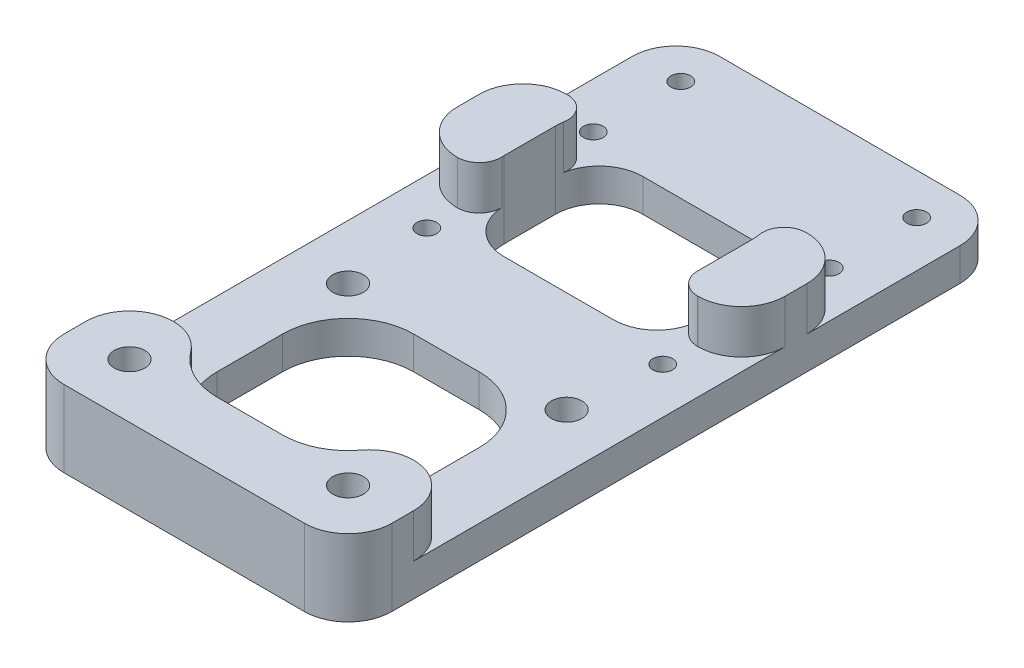
SolidWorks part; units mm, degrees
ref_plane "Front Plane" through (0, 0, 0) normal (0, 0, 1) x (1, 0, 0)
ref_plane "Top Plane" through (0, 0, 0) normal (0, 1, 0) x (1, 0, 0)
ref_plane "Right Plane" through (0, 0, 0) normal (1, 0, 0) x (0, 0, -1)
sketch "Sketch1" plane through (0, 0, 0) normal (0, 1, 0) x (1, 0, 0)
  line L1 (-15, -15) -> (15, -15)
  line L2 (-15, -15) -> (-15, 15)
  line L3 (-15, 15) -> (15, 15)
  line L4 (15, -15) -> (15, 15)
  line L5 (-15, -15) -> (15, 15) construction
  line L6 (-15, 15) -> (15, -15) construction
  point P0 (0, 0)
  dimension "D1" = 30
extrude "Boss-Extrude1" add sketch "Sketch1" along normal blind 3
sketch "Sketch3" plane through (0, 3, 0) normal (0, 1, 0) x (1, 0, 0)
  line L0 (15, -15) -> (15, 15) construction
  line L1 (-15, 15) -> (15, 15)
  line L2 (-15, 15) -> (-15, 45)
  line L3 (-15, 45) -> (15, 45)
  line L4 (15, 15) -> (15, 45)
  point P5 (0, 0)
  dimension "D1" = 30
extrude "Boss-Extrude2" add sketch "Sketch3" against normal up to surface (3 mm away) up to face at (0, 0, 0)
sketch "Sketch4" plane through (0, 3, 0) normal (0, 1, 0) x (1, 0, 0)
  line L0 (15, -15) -> (15, 45) construction
  line L1 (-15, -15) -> (15, -15)
  line L2 (-15, -15) -> (-15, -5)
  line L3 (-15, -5) -> (15, -5)
  line L4 (15, -15) -> (15, -5)
  line L5 (-15, 45) -> (-15, -15) construction
  line L6 (15, 31) -> (-15, 31)
  line L7 (15, 31) -> (15, 21)
  line L8 (15, 21) -> (-15, 21)
  line L9 (-15, 31) -> (-15, 21)
  line L10 (15, 45) -> (-15, 45) construction
  dimension "D1" = 10
  dimension "D2" = 10
  dimension "D3" = 14
extrude "Boss-Extrude3" add sketch "Sketch4" along normal blind 4 contours L3 L4 L1 L2 | L7 L6 L9 L8
sketch "Sketch2" plane through (0, 3, 0) normal (0, 1, 0) x (1, 0, 0)
  line L0 (0, 0) -> (0, 50000) construction
  line L1 (-10, -10) -> (10, -10) construction
  line L2 (-10, -10) -> (-10, 10) construction
  line L3 (-10, 10) -> (10, 10) construction
  line L4 (10, -10) -> (10, 10) construction
  line L5 (-10, -10) -> (10, 10) construction
  line L6 (-10, 10) -> (10, -10) construction
  line L7 (-3, -9) -> (3, -9)
  line L8 (-9, -3) -> (-9, 3)
  line L9 (-3, 9) -> (3, 9)
  line L10 (9, -3) -> (9, 3)
  line L11 (-9, -9) -> (10.9087, 10.9087) construction
  line L12 (-9, 9) -> (9, -9) construction
  line L13 (0, 25.62) -> (50000, 25.62) construction
  line L15 (-10.795, 18) -> (10.795, 18) construction
  line L16 (-10.795, 18) -> (-10.795, 33.24) construction
  line L17 (-10.795, 33.24) -> (10.795, 33.24) construction
  line L18 (10.795, 18) -> (10.795, 33.24) construction
  line L19 (-10.795, 18) -> (10.795, 33.24) construction
  line L20 (-10.795, 33.24) -> (10.795, 18) construction
  line L21 (-10.795, 41.24) -> (10.795, 41.24) construction
  line L22 (-10.795, 41.24) -> (-10.795, 33.24) construction
  line L23 (-10.795, 33.24) -> (10.795, 33.24) construction
  line L24 (10.795, 41.24) -> (10.795, 33.24) construction
  line L25 (-10.795, 41.24) -> (10.795, 33.24) construction
  line L26 (-10.795, 33.24) -> (10.795, 41.24) construction
  line L28 (-5, 19.2671) -> (5, 19.2671)
  line L29 (-9, 23.2671) -> (-9, 27.9729)
  line L30 (-5, 31.9729) -> (5, 31.9729)
  line L31 (9, 23.2671) -> (9, 27.9729)
  line L32 (-9, 19.2671) -> (9, 31.9729) construction
  line L33 (-9, 31.9729) -> (9, 19.2671) construction
  circle A0 centre (-10, -10) radius 1.4
  circle A1 centre (10, -10) radius 1.4
  circle A2 centre (10, 10) radius 1.4
  circle A3 centre (-10, 10) radius 1.4
  arc A4 (-3, -9) -> (-9, -3) centre (-3, -3) cw
  arc A5 (3, -9) -> (9, -3) centre (3, -3) ccw
  arc A6 (3, 9) -> (9, 3) centre (3, 3) cw
  arc A7 (-9, 3) -> (-3, 9) centre (-3, 3) cw
  circle A8 centre (-10.795, 33.24) radius 0.9
  circle A9 centre (10.795, 33.24) radius 0.9
  circle A10 centre (10.795, 18) radius 0.9
  circle A11 centre (-10.795, 18) radius 0.9
  circle A12 centre (-10.795, 41.24) radius 0.9
  circle A13 centre (10.795, 41.24) radius 0.9
  arc A14 (-5, 19.2671) -> (-9, 23.2671) centre (-5, 23.2671) cw
  arc A15 (5, 31.9729) -> (9, 27.9729) centre (5, 27.9729) cw
  arc A16 (5, 19.2671) -> (9, 23.2671) centre (5, 23.2671) ccw
  arc A17 (-9, 27.9729) -> (-5, 31.9729) centre (-5, 27.9729) cw
  point P0 (0, 0)
  point P10 (0, 0)
  point P31 (0, 25.62)
  point P40 (0, 37.24)
  point P44 (0, 0)
  point P45 (8.3791, 2.3791)
  point P47 (0, 25.62)
  dimension "D2" = 2.8
  dimension "D4" = 6
  dimension "D9" = 4
  dimension "D3" = 1.8
  dimension "D1" = 20
  dimension "D5" = 21.59
  dimension "D6" = 15.24
  dimension "D7" = 8
  dimension "D8" = 8
  dimension "D10" = 18
extrude "Cut-Extrude1" cut sketch "Sketch2" along normal through all both and the other way through all
fillet "Fillet1" radius 4 12 edges at (-15, 1.5, -45) (15, 1.5, -45) (15, 3.5, 15) (-15, 3.5, 15) (15, 5, 5) (8.6569, 5, 5) (-8.6569, 5, 5) (-15, 5, 5) (15, 5, -21) (15, 5, -31) (-15, 5, -21) (-15, 5, -31)
fillet "Fillet2" radius 2 4 edges at (-8.2955, 5, -21) (-7.6147, 5, -31) (8.2955, 5, -21) (7.6147, 5, -31)
